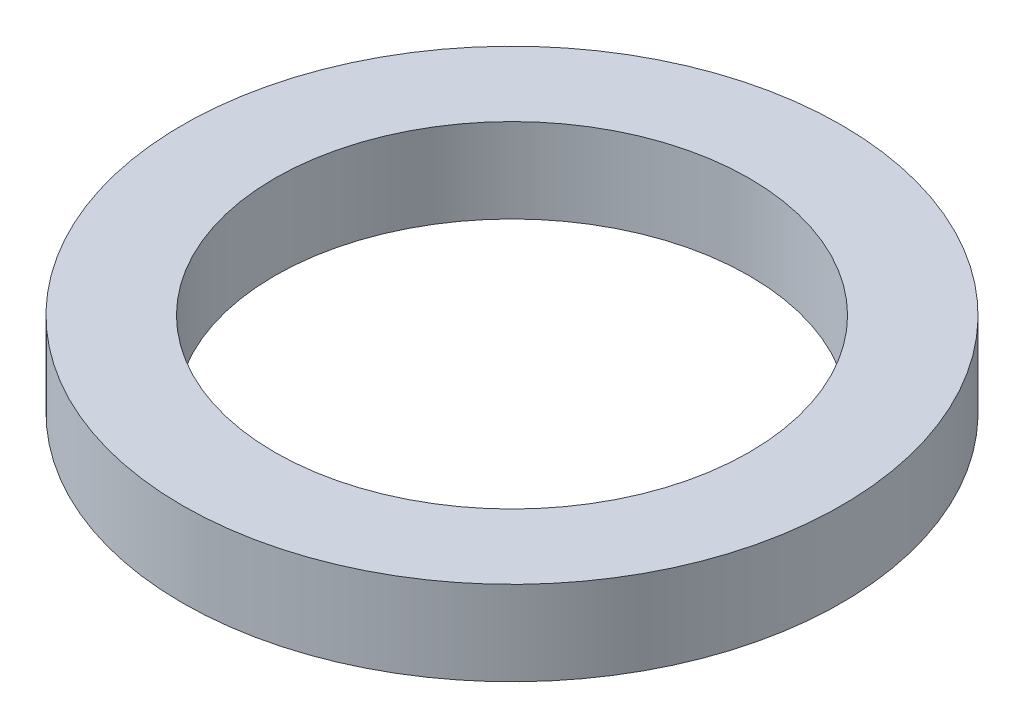
SolidWorks part; units mm, degrees
ref_plane "Front Plane" through (0, 0, 0) normal (0, 0, 1) x (1, 0, 0)
ref_plane "Top Plane" through (0, 0, 0) normal (0, 1, 0) x (1, 0, 0)
ref_plane "Right Plane" through (0, 0, 0) normal (1, 0, 0) x (0, 0, -1)
sketch "Sketch1" plane through (0, 0, 0) normal (0, 1, 0) x (1, 0, 0)
  circle A0 centre (0, 0) radius 62.5
  dimension "FLANGE_OD" = 125
extrude "Boss-Extrude1" add sketch "Sketch1" along normal blind 16
sketch "Sketch2" plane through (0, 0, 0) normal (0, 1, 0) x (1, 0, 0)
  circle A0 centre (0, 0) radius 45
  dimension "BORE_D" = 90
extrude "Cut-Extrude1" cut sketch "Sketch2" along normal through all
sketch "Sketch3" plane through (0, 16, 0) normal (0, 1, 0) x (1, 0, 0)
  circle A0 centre (0, 0) radius 24.8427 construction
  circle A1 centre (-24.8427, 0) radius 2.4015
  dimension "BOLT_D" = 4.8029
  dimension "BOLT_PCD" = 49.6853
extrude "Cut-Extrude2" cut sketch "Sketch3" against normal blind 14.347 rebuild error yes
pattern_circular "CirPattern1" count 5 over 360 rebuild error yes
